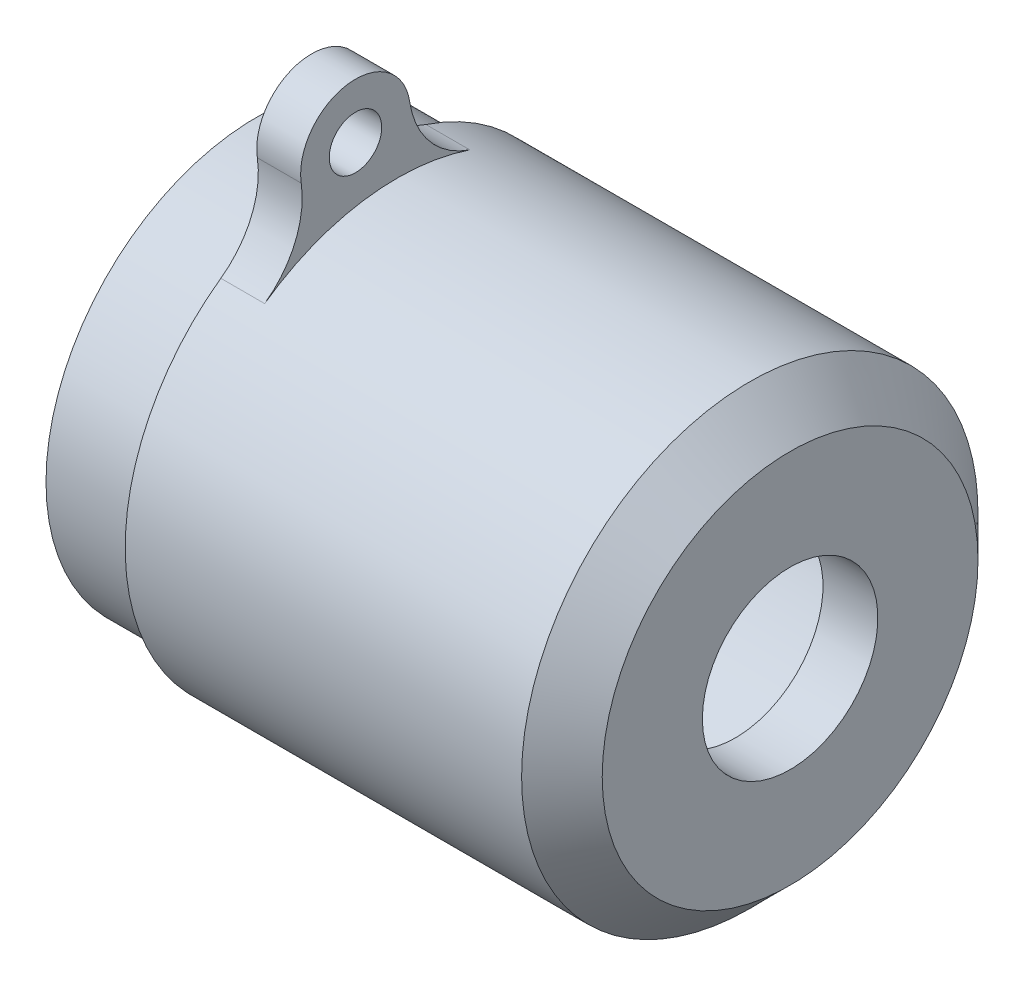
SolidWorks part; units mm, degrees
material "6061-T6 (SS)"
ref_plane "Front Plane" through (0, 0, 0) normal (0, 0, 1) x (1, 0, 0)
ref_plane "Top Plane" through (0, 0, 0) normal (0, 1, 0) x (1, 0, 0)
ref_plane "Right Plane" through (0, 0, 0) normal (1, 0, 0) x (0, 0, -1)
other "Center of Mass"
sketch "Sketch1" plane through (-25.4, 0, 0) normal (1, 0, 0) x (0, 0, -1)
  line L0 (0, 0) -> (-3.0235, 20.259) construction
  line L1 (-0.1715, 16.6719) -> (1.509, 20.9354) construction
  line L2 (1.509, 20.9354) -> (-1.3431, 24.5225) construction
  line L3 (-1.3431, 24.5225) -> (-5.8756, 23.846) construction
  line L4 (-5.8756, 23.846) -> (-7.5561, 19.5825) construction
  line L5 (-7.5561, 19.5825) -> (-4.704, 15.9955) construction
  line L6 (-4.704, 15.9955) -> (-0.1715, 16.6719) construction
  line L7 (4.704, -15.9955) -> (0.1715, -16.6719) construction
  line L8 (0.1715, -16.6719) -> (-1.509, -20.9354) construction
  line L9 (-1.509, -20.9354) -> (1.3431, -24.5225) construction
  line L10 (1.3431, -24.5225) -> (5.8756, -23.846) construction
  line L11 (5.8756, -23.846) -> (7.5561, -19.5825) construction
  line L12 (7.5561, -19.5825) -> (4.704, -15.9955) construction
  line L13 (-6.9488, 19.6731) -> (0.9017, 20.8448) construction
  line L15 (0, 0) -> (28.5651, 4.2632) construction
  circle A0 centre (0, 0) radius 13.9746
  circle A1 centre (0, 0) radius 16.5146 construction
  circle A2 centre (-3.0235, 20.259) radius 3.9687 construction
  circle A3 centre (3.0235, -20.259) radius 3.9687 construction
  circle A4 centre (-3.0235, 20.259) radius 8.6143 construction
  arc A8 (-9.5934, 13.4424) -> (-5.2504, -15.6578) centre (0, 0) ccw
  arc A9 (5.2504, 15.6578) -> (9.5934, -13.4424) centre (0, 0) cw
  circle A16 centre (-3.0235, 20.259) radius 2.667 construction
  circle A17 centre (3.0235, -20.259) radius 2.667 construction
  arc A18 (-9.6563, 36.4316) -> (-11.3683, 23.9475) centre (128.3504, 11.1461) ccw construction
  arc A19 (4.4855, 36.4316) -> (4.6428, 28.4562) centre (76.9323, 33.8717) ccw construction
  arc A20 (-9.5934, 13.4424) -> (-6.9488, 19.6731) centre (-13.3575, 18.7167) ccw
  arc A21 (-6.9488, 19.6731) -> (0.9017, 20.8448) centre (-3.0235, 20.259) cw
  arc A22 (0.9017, 20.8448) -> (5.2504, 15.6578) centre (7.3104, 21.8013) ccw
  arc A23 (6.9488, -19.6731) -> (9.5934, -13.4424) centre (13.3575, -18.7167) cw
  arc A24 (-0.9017, -20.8448) -> (6.9488, -19.6731) centre (3.0235, -20.259) ccw
  arc A25 (-5.2504, -15.6578) -> (-0.9017, -20.8448) centre (-7.3104, -21.8013) cw
  point P38 (-4.9373, -15.7718)
  point P47 (9.7948, -13.4424)
  dimension "D1" = 27.9492
  dimension "D4" = 5.334
  dimension "D2" = 2.54
  dimension "D3" = 7.9375
extrude "Boss-Extrude1" add sketch "Sketch1" along normal blind 3.175
sketch "Sketch2" plane through (-22.225, 0, 0) normal (1, 0, 0) x (0, 0, -1)
  circle A0 centre (0, 0) radius 13.9746
  circle A1 centre (0, 0) radius 16.5146
  arc A2 (-9.5934, 13.4424) -> (-5.2504, -15.6578) centre (0, 0) ccw construction
  circle A3 centre (0, 0) radius 13.9746 construction
extrude "Boss-Extrude2" add sketch "Sketch2" along normal up to surface (24.4625 mm away)
sketch "Sketch5" plane through (0, 0, 0) normal (0, 0, 1) x (1, 0, 0)
  line L1 (6.2063, 13.598) -> (6.2063, 6.35)
  line L3 (2.2375, -16.5146) -> (2.2375, 16.5146) construction
  line L4 (2.2375, 6.35) -> (2.2375, 16.5146)
  line L5 (0, 0) -> (45.5597, 0) construction
  line L6 (2.2375, 6.35) -> (6.2063, 6.35)
  line L7 (2.2375, 16.5146) -> (3.2896, 16.5146)
  line L8 (3.2896, 16.5146) -> (6.2063, 13.598)
  line L9 (2.2375, 13.9746) -> (4.0336, 15.7707) construction
  point P10 (0, 0)
  dimension "D2" = 3.9688
  dimension "D1" = 12.7
  dimension "D3" = 45
  dimension "D4" = 2.54
  dimension "D5" = 2.54
revolve "Revolve1" add sketch "Sketch5" angle 360 about L5
sketch "Sketch3" plane through (-25.4, 0, 0) normal (-1, 0, 0) x (0, 0, 1)
  circle A0 centre (0, 0) radius 13.9746
  circle A1 centre (0, 0) radius 15.2446
  circle A2 centre (0, 0) radius 13.9746 construction
  dimension "D1" = 1.27
extrude "Boss-Extrude3" add sketch "Sketch3" along normal blind 7
sketch "Sketch6" plane through (0, 0, 0) normal (0, 0, 1) x (1, 0, 0)
  line L0 (-25.4, -24.2277) -> (-24.8262, -24.2277)
  line L1 (-25.4, -24.2277) -> (-22.225, -24.2277) construction
  line L2 (-25.4, -24.2277) -> (-25.4, -21.59)
  line L3 (-25.4, -19.6731) -> (-25.4, -24.2277) construction
  arc A0 (-25.4, -21.59) -> (-22.3418, -27.0202) centre (-19.05, -21.59) ccw construction
  arc A1 (-24.8262, -24.2277) -> (-25.4, -21.59) centre (-19.05, -21.59) cw
extrude "Cut-Extrude1" cut sketch "Sketch6" against normal through all both and the other way through all
hole_wizard "#6 Clearance Hole1" positions "Sketch7" profile "Sketch8" hole size "#6" standard "ANSI Inch" end condition up to next
sketch "Sketch7" plane through (-22.225, 0, 0) normal (1, 0, 0) x (0, 0, -1)
  point P0 (-3.0235, 20.259)
  point P3 (3.0235, -20.259)
sketch "Sketch8" plane through (-22.225, 20.259, 3.0235) normal (0, 1, 0) x (0, 0, -1)
  line L0 (0, 0) -> (0, 3.175)
  line L1 (0, 3.175) -> (1.8986, 3.175)
  line L2 (1.8986, 3.175) -> (1.8986, 0)
  line L5 (1.8986, 0) -> (0, 0)
  line L11 (0, -6.35) -> (0, 107.95) construction
  dimension "Thru Hole Dia." = 3.7973
  dimension "Thru Hole Depth" = 3.175
equation "\"motor diameter\"= 28mm"
equation "\"D1@Sketch1\"=\"motor diameter\"-0.002in"
equation "\"D1@Boss-Extrude3\"=7mm"
equation "\"D2@Sketch5\"=5/32"
